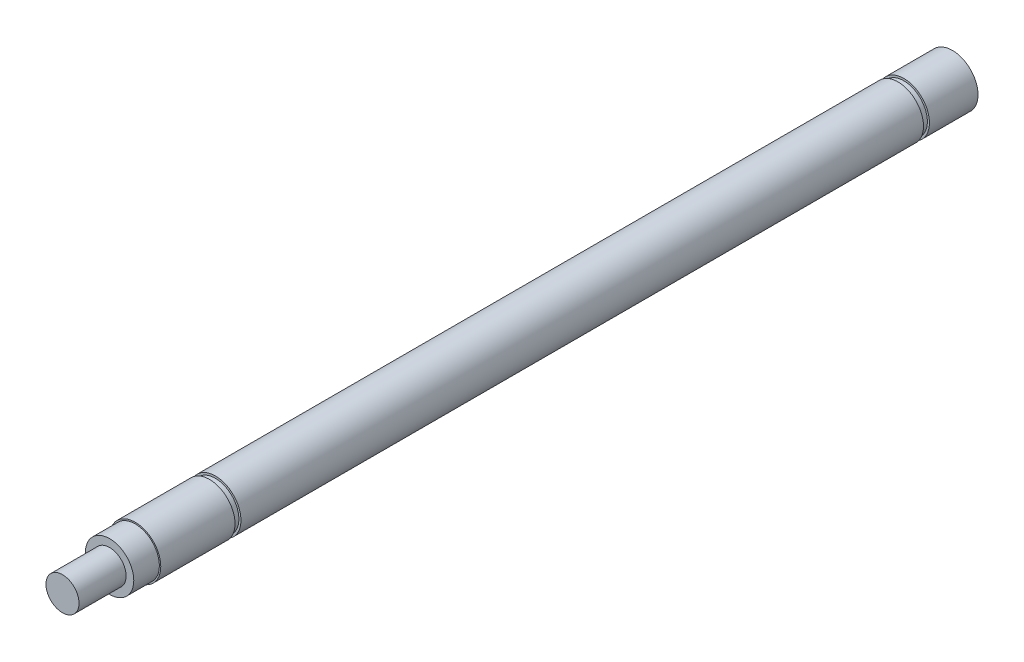
SolidWorks part; units mm, degrees
ref_plane "Front Plane" through (0, 0, 0) normal (0, 0, 1) x (1, 0, 0)
ref_plane "Top Plane" through (0, 0, 0) normal (0, 1, 0) x (1, 0, 0)
ref_plane "Right Plane" through (0, 0, 0) normal (1, 0, 0) x (0, 0, -1)
sketch "Sketch1" plane through (0, 0, 0) normal (0, 1, 0) x (1, 0, 0)
  line L0 (3.175, 99.7956) -> (-3.175, 99.7956) construction
  line L1 (4.915, -10.6045) -> (-4.915, -10.6045) construction
  line L2 (2.05, -1.5875) -> (2.05, -10.6045) construction
  line L3 (4.915, -4.7625) -> (-4.915, -4.7625) construction
  line L4 (3, -1.5875) -> (3, -4.7625) construction
  line L5 (3.175, -1.5875) -> (-3.175, -1.5875) construction
  line L6 (0, -1.5875) -> (0, 99.7956) construction
  line L7 (3.175, -1.5875) -> (3.175, 99.7956) construction
  line L8 (3.175, 99.7956) -> (0, 99.7956)
  line L9 (2.05, -10.6045) -> (0, -10.6045)
  line L10 (2.05, -4.7625) -> (2.05, -10.6045)
  line L11 (3, -4.7625) -> (2.05, -4.7625)
  line L12 (3, -1.5875) -> (3, -4.7625)
  line L13 (3.175, -1.5875) -> (3, -1.5875)
  line L14 (0, -10.6045) -> (0, 99.7956)
  line L15 (3.175, -1.5875) -> (3.175, 7.62)
  line L16 (3.175, 7.62) -> (2.921, 7.62) construction
  line L17 (2.921, 7.62) -> (2.921, 8.3566) construction
  line L18 (3.175, 8.3566) -> (2.921, 8.3566) construction
  line L19 (3.175, 93.0328) -> (2.921, 93.0328) construction
  line L20 (2.921, 93.7694) -> (2.921, 93.0328) construction
  line L21 (3.175, 93.7694) -> (2.921, 93.7694) construction
  line L22 (3.175, 7.62) -> (2.921, 7.62)
  line L23 (2.921, 7.62) -> (2.921, 8.3566)
  line L24 (3.175, 8.3566) -> (2.921, 8.3566)
  line L25 (3.175, 93.0328) -> (2.921, 93.0328)
  line L26 (2.921, 93.7694) -> (2.921, 93.0328)
  line L27 (3.175, 93.7694) -> (2.921, 93.7694)
  line L28 (3.175, 8.3566) -> (3.175, 93.0328)
  line L29 (3.175, 93.7694) -> (3.175, 99.7956)
revolve "Revolve1" add sketch "Sketch1" angle 360 about L14
